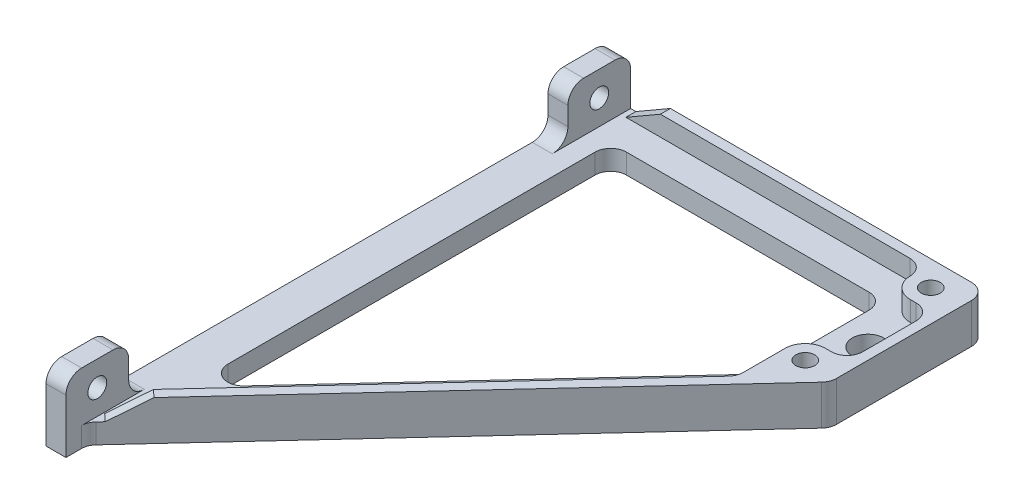
SolidWorks part; units mm, degrees
ref_plane "Front Plane" through (0, 0, 0) normal (0, 0, 1) x (1, 0, 0)
ref_plane "Top Plane" through (0, 0, 0) normal (0, 1, 0) x (1, 0, 0)
ref_plane "Right Plane" through (0, 0, 0) normal (1, 0, 0) x (0, 0, -1)
sketch "Sketch1" plane through (0, 0, 0) normal (0, 1, 0) x (1, 0, 0)
  line L0 (0, 0) -> (120, 0)
  line L1 (120, 0) -> (120, -50)
  line L2 (120, -50) -> (6.35, -173.1208)
  line L3 (0, -180) -> (0, 0)
  line L4 (110, 0) -> (110, -60.8333) construction
  line L5 (0, -180) -> (6.35, -180)
  line L6 (6.35, -180) -> (6.35, -173.1208)
  line L7 (6.35, -173.1208) -> (0, -180) construction
  dimension "D1" = 50
  dimension "D2" = 110
  dimension "D3" = 10
  dimension "D4" = 180
  dimension "D5" = 6.35
extrude "Boss-Extrude1" add sketch "Sketch1" along normal blind 6.35
sketch "Sketch2" plane through (0, 6.35, 0) normal (0, 1, 0) x (1, 0, 0)
  line L0 (110, -8) -> (110, -48) construction
  line L1 (100, -12.7) -> (100, -52.9428)
  line L2 (100, -12.7) -> (12.7, -12.7)
  line L3 (12.7, -12.7) -> (12.7, -147.5178)
  line L4 (12.7, -147.5178) -> (100, -52.9428)
  line L7 (0, 0) -> (0, -180)
  line L8 (0, -180) -> (6.35, -180)
  line L9 (6.35, -180) -> (6.35, -173.1208)
  line L10 (6.35, -173.1208) -> (120, -50)
  line L11 (120, -50) -> (120, 0)
  line L12 (120, 0) -> (0, 0)
  line L13 (0, 0) -> (0, -180)
  line L14 (0, -180) -> (6.35, -180)
  line L15 (6.35, -180) -> (6.35, -173.1208)
  line L16 (6.35, -173.1208) -> (120, -50)
  line L17 (120, -50) -> (120, 0)
  line L18 (120, 0) -> (0, 0)
  circle A0 centre (110, -8) radius 3
  circle A1 centre (110, -48) radius 3
  dimension "D4" = 6
  dimension "D1" = 40
  dimension "D2" = 110
  dimension "D3" = 8
  dimension "D6" = 12.7
  dimension "D7" = 12.7
  dimension "D8" = 12.7
  dimension "D5" = 0
extrude "Cut-Extrude3" cut sketch "Sketch2" against normal through all contours L1 L4 L3 L2 | A0 | A1
sketch "Sketch7" plane through (0, 6.35, 0) normal (0, 1, 0) x (1, 0, 0)
  line L0 (4.017, -170.9673) -> (116.825, -48.7586)
  line L1 (116.825, -48.7586) -> (116.825, -3.175)
  line L2 (116.825, -3.175) -> (4.017, -3.175)
  line L3 (4.017, -170.9673) -> (6.35, -173.1208)
  line L4 (3.175, -176.825) -> (3.175, -176.825)
  line L5 (4.017, -3.175) -> (4.017, 0)
  line L6 (0, 0) -> (0, -180)
  line L7 (0, -180) -> (6.35, -180)
  line L8 (6.35, -180) -> (6.35, -173.1208)
  line L9 (6.35, -173.1208) -> (120, -50)
  line L10 (120, -50) -> (120, 0)
  line L11 (120, 0) -> (0, 0)
  line L12 (0, 0) -> (0, -180)
  line L13 (0, -180) -> (6.35, -180)
  line L14 (6.35, -180) -> (6.35, -173.1208)
  line L15 (6.35, -173.1208) -> (120, -50)
  line L16 (120, -50) -> (120, 0)
  line L17 (120, 0) -> (0, 0)
  line L18 (116.825, -3.175) -> (3.175, -3.175) construction
  line L20 (3.175, -3.175) -> (3.175, -176.825) construction
  line L21 (3.175, -176.825) -> (3.175, -171.8795) construction
  line L22 (3.175, -171.8795) -> (116.825, -48.7586) construction
  point P12 (0, 0)
  dimension "D1" = 0
  dimension "D2" = 3.175
extrude "Boss-Extrude3" add sketch "Sketch7" along normal blind 6.35
chamfer "Chamfer1" distance 15 angle 30 2 edges at (5.1835, 12.7, 172.0441) (4.017, 12.7, 1.5875) first distance on face at (61.5064, 12.7, 56.1496)
sketch "Sketch8" plane through (0, 6.35, 0) normal (0, 1, 0) x (1, 0, 0)
  line L0 (110, -14.5) -> (116.825, -14.5)
  line L1 (116.825, -48.7586) -> (116.825, -3.175) construction
  line L2 (103.5, -8) -> (103.5, -3.175)
  line L3 (116.825, -3.175) -> (8.0185, -3.175) construction
  line L4 (103.5, -3.175) -> (116.825, -3.175)
  line L5 (116.825, -3.175) -> (116.825, -14.5)
  line L6 (110, -41.5) -> (116.825, -41.5)
  line L7 (103.5, -48) -> (103.5, -63.194)
  line L8 (6.7311, -168.027) -> (116.825, -48.7586) construction
  line L9 (116.825, -41.5) -> (116.825, -48.7586)
  line L10 (116.825, -48.7586) -> (103.5, -63.194)
  circle A0 centre (110, -48) radius 3 construction
  circle A1 centre (110, -8) radius 3 construction
  circle A2 centre (110, -48) radius 3
  circle A3 centre (110, -8) radius 3
  arc A4 (103.5, -8) -> (110, -14.5) centre (110, -8) ccw
  arc A5 (110, -41.5) -> (103.5, -48) centre (110, -48) ccw
  dimension "D1" = 3.5
extrude "Boss-Extrude4" add sketch "Sketch8" along normal blind 6.35
sketch "Sketch9" plane through (0, 6.35, 0) normal (0, 1, 0) x (1, 0, 0)
  line L0 (6.35, -180) -> (6.35, -173.1208) construction
  line L1 (0, 0) -> (6.35, 0)
  line L2 (0, 0) -> (0, -20)
  line L3 (0, -20) -> (6.35, -20)
  line L4 (6.35, 0) -> (6.35, -20)
  line L5 (0, -180) -> (6.35, -180)
  line L6 (0, -180) -> (0, -160)
  line L7 (0, -160) -> (6.35, -160)
  line L8 (6.35, -180) -> (6.35, -160)
  dimension "D1" = 20
extrude "Boss-Extrude5" add sketch "Sketch9" along normal blind 15.875
sketch "Sketch10" plane through (6.35, 0, 0) normal (1, 0, 0) x (0, 0, -1)
  line L0 (-20, 22.225) -> (0, 6.35) construction
  line L1 (-180, 22.225) -> (-160, 6.35) construction
  circle A0 centre (-10, 14.2875) radius 3
  circle A1 centre (-170, 14.2875) radius 3
  dimension "D1" = 6
extrude "Cut-Extrude4" cut sketch "Sketch10" against normal blind 110.875
fillet "Fillet3" radius 5 17 edges at (103.5, 9.525, 63.194) (116.825, 9.525, 41.5) (116.825, 9.525, 14.5) (103.5, 9.525, 3.175) (120, 6.35, 0) (120, 6.35, 50) (6.35, 3.175, 173.1208) (12.7, 3.175, 147.5178) (100, 3.175, 52.9428) (100, 3.175, 12.7) (12.7, 3.175, 12.7) (3.175, 22.225, 180) (3.175, 6.35, 160) (3.175, 22.225, 160) (3.175, 22.225, 0) (3.175, 22.225, 20) (3.175, 6.35, 20)
sketch "Sketch11" plane through (0, 6.35, 0) normal (0, 1, 0) x (1, 0, 0)
  line L0 (110, -8) -> (110, -48) construction
  circle A0 centre (110, -28) radius 5
  dimension "D1" = 10
extrude "Cut-Extrude5" cut sketch "Sketch11" against normal blind 15.875
